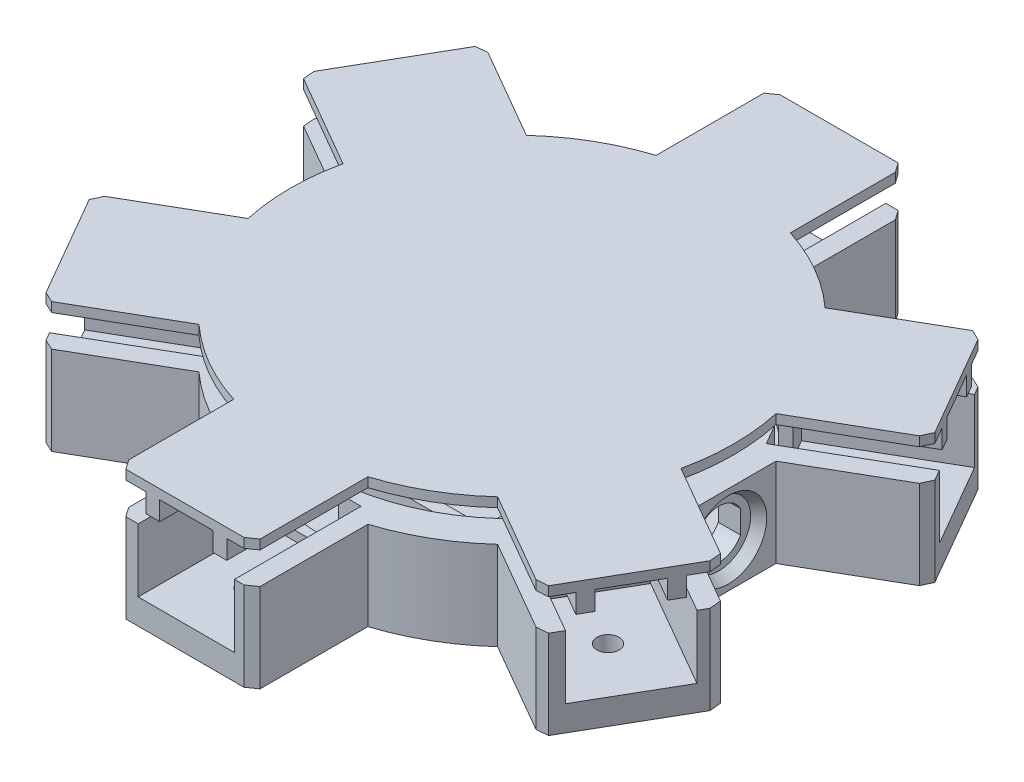
SolidWorks part; units mm, degrees
ref_plane "Front" through (0, 0, 0) normal (0, 0, 1) x (1, 0, 0)
ref_plane "Top" through (0, 0, 0) normal (0, 1, 0) x (1, 0, 0)
ref_plane "Right" through (0, 0, 0) normal (1, 0, 0) x (0, 0, -1)
sketch "Эскиз1" plane through (0, 0, 0) normal (0, 1, 0) x (1, 0, 0)
  line L0 (0, 0) -> (0, 74.8456) construction
  line L1 (63.5176, 45.4476) -> (11.5561, 15.4476) construction
  line L2 (-7.6, 77.7316) -> (7.6, 77.7316) construction
  line L3 (-7.6, 77.7316) -> (-7.6, 17.7316) construction
  line L4 (-7.6, 17.7316) -> (7.6, 17.7316) construction
  line L5 (7.6, 77.7316) -> (7.6, 17.7316) construction
  line L6 (0, 17.7316) -> (0, 77.7316) construction
  line L7 (-7.6, 47.7316) -> (7.6, 47.7316) construction
  line L8 (63.5176, 45.4476) -> (71.1176, 32.284) construction
  line L9 (0, 0) -> (64.8182, 37.4228) construction
  line L10 (71.1176, 32.284) -> (19.1561, 2.284) construction
  line L11 (11.5561, 15.4476) -> (19.1561, 2.284) construction
  line L12 (71.1176, -32.284) -> (19.1561, -2.284) construction
  line L13 (71.1176, -32.284) -> (63.5176, -45.4476) construction
  line L14 (0, 0) -> (64.8182, -37.4228) construction
  line L15 (63.5176, -45.4476) -> (11.5561, -15.4476) construction
  line L16 (19.1561, -2.284) -> (11.5561, -15.4476) construction
  line L17 (7.6, -77.7316) -> (7.6, -17.7316) construction
  line L18 (7.6, -77.7316) -> (-7.6, -77.7316) construction
  line L19 (0, 0) -> (0, -74.8456) construction
  line L20 (-7.6, -77.7316) -> (-7.6, -17.7316) construction
  line L21 (7.6, -17.7316) -> (-7.6, -17.7316) construction
  line L22 (-63.5176, -45.4476) -> (-11.5561, -15.4476) construction
  line L23 (-63.5176, -45.4476) -> (-71.1176, -32.284) construction
  line L24 (0, 0) -> (-64.8182, -37.4228) construction
  line L25 (-71.1176, -32.284) -> (-19.1561, -2.284) construction
  line L26 (-11.5561, -15.4476) -> (-19.1561, -2.284) construction
  line L27 (-71.1176, 32.284) -> (-19.1561, 2.284) construction
  line L28 (-71.1176, 32.284) -> (-63.5176, 45.4476) construction
  line L29 (0, 0) -> (-64.8182, 37.4228) construction
  line L30 (-63.5176, 45.4476) -> (-11.5561, 15.4476) construction
  line L31 (-19.1561, 2.284) -> (-11.5561, 15.4476) construction
  line L32 (0, 31.44) -> (-11.5561, 31.44) construction
  line L33 (-7.6, 31.44) -> (-7.6, 51.44)
  line L34 (-7.6, 51.44) -> (-10.6, 51.44)
  line L35 (-10.6, 51.44) -> (-10.6, 33.3563)
  line L36 (0, 31.44) -> (11.9132, 31.44) construction
  line L38 (7.6, 31.44) -> (7.6, 51.44)
  line L39 (7.6, 51.44) -> (10.6, 51.44)
  line L40 (10.6, 51.44) -> (10.6, 33.3563)
  line L42 (-7.6, 31.44) -> (7.6, 31.44)
  line L43 (39.2483, 34.8999) -> (23.5874, 25.858)
  line L44 (23.4278, 22.3018) -> (40.7483, 32.3018)
  line L45 (40.7483, 32.3018) -> (39.2483, 34.8999)
  line L46 (48.3483, 19.1382) -> (49.8483, 16.5401)
  line L47 (31.0278, 9.1382) -> (48.3483, 19.1382)
  line L48 (49.8483, 16.5401) -> (34.1874, 7.4983)
  line L49 (23.4278, 22.3018) -> (31.0278, 9.1382)
  line L50 (49.8483, -16.5401) -> (34.1874, -7.4983)
  line L51 (31.0278, -9.1382) -> (48.3483, -19.1382)
  line L52 (48.3483, -19.1382) -> (49.8483, -16.5401)
  line L53 (40.7483, -32.3018) -> (39.2483, -34.8999)
  line L54 (23.4278, -22.3018) -> (40.7483, -32.3018)
  line L55 (39.2483, -34.8999) -> (23.5874, -25.858)
  line L56 (31.0278, -9.1382) -> (23.4278, -22.3018)
  line L57 (10.6, -51.44) -> (10.6, -33.3563)
  line L58 (7.6, -31.44) -> (7.6, -51.44)
  line L59 (7.6, -51.44) -> (10.6, -51.44)
  line L60 (-7.6, -51.44) -> (-10.6, -51.44)
  line L61 (-7.6, -31.44) -> (-7.6, -51.44)
  line L62 (-10.6, -51.44) -> (-10.6, -33.3563)
  line L63 (7.6, -31.44) -> (-7.6, -31.44)
  line L64 (-39.2483, -34.8999) -> (-23.5874, -25.858)
  line L65 (-23.4278, -22.3018) -> (-40.7483, -32.3018)
  line L66 (-40.7483, -32.3018) -> (-39.2483, -34.8999)
  line L67 (-48.3483, -19.1382) -> (-49.8483, -16.5401)
  line L68 (-31.0278, -9.1382) -> (-48.3483, -19.1382)
  line L69 (-49.8483, -16.5401) -> (-34.1874, -7.4983)
  line L70 (-23.4278, -22.3018) -> (-31.0278, -9.1382)
  line L71 (-49.8483, 16.5401) -> (-34.1874, 7.4983)
  line L72 (-31.0278, 9.1382) -> (-48.3483, 19.1382)
  line L73 (-48.3483, 19.1382) -> (-49.8483, 16.5401)
  line L74 (-40.7483, 32.3018) -> (-39.2483, 34.8999)
  line L75 (-23.4278, 22.3018) -> (-40.7483, 32.3018)
  line L76 (-39.2483, 34.8999) -> (-23.5874, 25.858)
  line L77 (-31.0278, 9.1382) -> (-23.4278, 22.3018)
  line L78 (34.1874, 7.4983) -> (34.1874, -7.4983)
  line L79 (29.1874, 6.9352) -> (29.1874, -6.9352)
  arc A0 (29.1874, 6.9352) -> (29.1874, -6.9352) centre (0, 0) ccw
  arc A1 (-10.6, 33.3563) -> (-23.5874, 25.858) centre (0, 0) ccw
  arc A2 (-34.1874, 7.4983) -> (-34.1874, -7.4983) centre (0, 0) ccw
  arc A3 (23.5874, 25.858) -> (10.6, 33.3563) centre (0, 0) ccw
  arc A4 (-23.5874, -25.858) -> (-10.6, -33.3563) centre (0, 0) ccw
  arc A5 (10.6, -33.3563) -> (23.5874, -25.858) centre (0, 0) ccw
  point P3 (0, 47.7316)
  dimension "D2" = 60
  dimension "D3" = 70
  dimension "D1" = 15.2
  dimension "D4" = 60
  dimension "D6" = 20
  dimension "D7" = 3
  dimension "D8" = 3
  dimension "D9" = 31.44
  dimension "D10" = 6
  dimension "D11" = 5
  dimension "D5" = 6
extrude "Бобышка-Вытянуть1" add sketch "Эскиз1" along normal blind 12
sketch "Эскиз2" plane through (0, 0, 0) normal (0, -1, 0) x (1, 0, 0)
  line L0 (-10.6, 51.44) -> (10.6, 51.44)
  line L1 (10.6, 51.44) -> (10.6, 33.3563)
  line L2 (-10.6, 51.44) -> (-10.6, 33.3563)
  line L3 (-23.5874, 25.858) -> (-39.2483, 34.8999)
  line L4 (-39.2483, 34.8999) -> (-49.8483, 16.5401)
  line L5 (-49.8483, 16.5401) -> (-34.1874, 7.4983)
  line L6 (-34.1874, -7.4983) -> (-49.8483, -16.5401)
  line L7 (-49.8483, -16.5401) -> (-48.3483, -19.1382)
  line L8 (-48.3483, -19.1382) -> (-39.2483, -34.8999)
  line L9 (-39.2483, -34.8999) -> (-23.5874, -25.858)
  line L10 (-10.6, -33.3563) -> (-10.6, -51.44)
  line L11 (-10.6, -51.44) -> (10.6, -51.44)
  line L12 (10.6, -51.44) -> (10.6, -33.3563)
  line L13 (23.5874, -25.858) -> (39.2483, -34.8999)
  line L14 (39.2483, -34.8999) -> (49.8483, -16.5401)
  line L15 (49.8483, -16.5401) -> (34.1874, -7.4983)
  line L16 (34.1874, -7.4983) -> (34.1874, 7.4983)
  line L17 (34.1874, 7.4983) -> (49.8483, 16.5401)
  line L18 (49.8483, 16.5401) -> (39.2483, 34.8999)
  line L19 (39.2483, 34.8999) -> (23.5874, 25.858)
  arc A0 (-34.1874, 7.4983) -> (-34.1874, -7.4983) centre (0, 0) ccw
  arc A1 (-10.6, 33.3563) -> (-23.5874, 25.858) centre (0, 0) ccw
  arc A2 (23.5874, 25.858) -> (10.6, 33.3563) centre (0, 0) ccw
  arc A3 (-23.5874, -25.858) -> (-10.6, -33.3563) centre (0, 0) ccw
  arc A4 (10.6, -33.3563) -> (23.5874, -25.858) centre (0, 0) ccw
extrude "Бобышка-Вытянуть2" add sketch "Эскиз2" along normal blind 2
sketch "Эскиз3" plane through (0, 0, 0) normal (0, 1, 0) x (1, 0, 0)
  line L0 (0, 31.44) -> (0, 51.44) construction
  line L1 (-7.6, 51.44) -> (7.6, 51.44)
  line L2 (-7.6, 51.44) -> (-7.6, 31.44)
  line L3 (-7.6, 31.44) -> (7.6, 31.44)
  line L4 (7.6, 51.44) -> (7.6, 31.44)
  line L5 (40.7483, 32.3018) -> (48.3483, 19.1382)
  line L6 (40.7483, 32.3018) -> (23.4278, 22.3018)
  line L7 (23.4278, 22.3018) -> (31.0278, 9.1382)
  line L8 (48.3483, 19.1382) -> (31.0278, 9.1382)
  line L9 (27.2278, 15.72) -> (44.5483, 25.72) construction
  line L10 (48.3483, -19.1382) -> (40.7483, -32.3018)
  line L11 (48.3483, -19.1382) -> (31.0278, -9.1382)
  line L12 (31.0278, -9.1382) -> (23.4278, -22.3018)
  line L13 (40.7483, -32.3018) -> (23.4278, -22.3018)
  line L14 (27.2278, -15.72) -> (44.5483, -25.72) construction
  line L15 (7.6, -51.44) -> (-7.6, -51.44)
  line L16 (7.6, -51.44) -> (7.6, -31.44)
  line L17 (7.6, -31.44) -> (-7.6, -31.44)
  line L18 (-7.6, -51.44) -> (-7.6, -31.44)
  line L19 (0, -31.44) -> (0, -51.44) construction
  line L20 (-40.7483, -32.3018) -> (-48.3483, -19.1382)
  line L21 (-40.7483, -32.3018) -> (-23.4278, -22.3018)
  line L22 (-23.4278, -22.3018) -> (-31.0278, -9.1382)
  line L23 (-48.3483, -19.1382) -> (-31.0278, -9.1382)
  line L24 (-27.2278, -15.72) -> (-44.5483, -25.72) construction
  line L25 (-48.3483, 19.1382) -> (-40.7483, 32.3018)
  line L26 (-48.3483, 19.1382) -> (-31.0278, 9.1382)
  line L27 (-31.0278, 9.1382) -> (-23.4278, 22.3018)
  line L28 (-40.7483, 32.3018) -> (-23.4278, 22.3018)
  line L29 (-27.2278, 15.72) -> (-44.5483, 25.72) construction
  circle A0 centre (0, 41.44) radius 1.75
  circle A1 centre (35.8881, 20.72) radius 1.75
  circle A2 centre (35.8881, -20.72) radius 1.75
  circle A3 centre (0, -41.44) radius 1.75
  circle A4 centre (-35.8881, -20.72) radius 1.75
  circle A5 centre (-35.8881, 20.72) radius 1.75
  dimension "D1" = 3.5
  dimension "D2" = 6
extrude "Бобышка-Вытянуть3" add sketch "Эскиз3" along normal blind 2
sketch "Эскиз4" plane through (0, 12, 0) normal (0, 1, 0) x (1, 0, 0)
  line L0 (0, 31.44) -> (0, 28.9927) construction
  line L1 (7.6, 31.44) -> (-7.6, 31.44) construction
  line L2 (25.6064, 19.4027) -> (29.6064, 12.4745)
  line L3 (-4, 31.8771) -> (4, 31.8771)
  line L4 (-4, 31.8771) -> (-4, 28.5556)
  line L5 (-4, 28.5556) -> (4, 28.5556)
  line L6 (4, 31.8771) -> (4, 28.5556)
  line L7 (0, 28.5556) -> (0, 31.8771) construction
  line L8 (-4, 30.2163) -> (4, 30.2163) construction
  line L9 (25.6064, 19.4027) -> (22.7298, 17.7419)
  line L10 (22.7298, 17.7419) -> (26.7298, 10.8137)
  line L11 (29.6064, 12.4745) -> (26.7298, 10.8137)
  line L12 (27.2278, 15.72) -> (25.1084, 14.4963) construction
  line L13 (24.7298, 14.2778) -> (27.6064, 15.9386) construction
  line L14 (24.1681, 18.5723) -> (28.1681, 11.6441) construction
  line L15 (29.6064, -12.4745) -> (25.6064, -19.4027)
  line L16 (29.6064, -12.4745) -> (26.7298, -10.8137)
  line L17 (26.7298, -10.8137) -> (22.7298, -17.7419)
  line L18 (25.6064, -19.4027) -> (22.7298, -17.7419)
  line L19 (27.2278, -15.72) -> (25.1084, -14.4963) construction
  line L20 (24.7298, -14.2778) -> (27.6064, -15.9386) construction
  line L21 (28.1681, -11.6441) -> (24.1681, -18.5723) construction
  line L22 (4, -31.8771) -> (-4, -31.8771)
  line L23 (4, -31.8771) -> (4, -28.5556)
  line L24 (4, -28.5556) -> (-4, -28.5556)
  line L25 (-4, -31.8771) -> (-4, -28.5556)
  line L26 (0, -31.44) -> (0, -28.9927) construction
  line L27 (0, -28.5556) -> (0, -31.8771) construction
  line L28 (4, -30.2163) -> (-4, -30.2163) construction
  line L29 (-25.6064, -19.4027) -> (-29.6064, -12.4745)
  line L30 (-25.6064, -19.4027) -> (-22.7298, -17.7419)
  line L31 (-22.7298, -17.7419) -> (-26.7298, -10.8137)
  line L32 (-29.6064, -12.4745) -> (-26.7298, -10.8137)
  line L33 (-27.2278, -15.72) -> (-25.1084, -14.4963) construction
  line L34 (-24.7298, -14.2778) -> (-27.6064, -15.9386) construction
  line L35 (-24.1681, -18.5723) -> (-28.1681, -11.6441) construction
  line L36 (-29.6064, 12.4745) -> (-25.6064, 19.4027)
  line L37 (-29.6064, 12.4745) -> (-26.7298, 10.8137)
  line L38 (-26.7298, 10.8137) -> (-22.7298, 17.7419)
  line L39 (-25.6064, 19.4027) -> (-22.7298, 17.7419)
  line L40 (-27.2278, 15.72) -> (-25.1084, 14.4963) construction
  line L41 (-24.7298, 14.2778) -> (-27.6064, 15.9386) construction
  line L42 (-28.1681, 11.6441) -> (-24.1681, 18.5723) construction
  point P5 (0, 30.2163)
  point P13 (26.1681, 15.1082)
  point P24 (26.1681, -15.1082)
  point P35 (0, -30.2163)
  point P46 (-26.1681, -15.1082)
  point P57 (-26.1681, 15.1082)
  dimension "D1" = 8
  dimension "D2" = 6
extrude "Вырез-Вытянуть1" cut sketch "Эскиз4" against normal blind 8.5
sketch "Эскиз5" plane through (34.1874, 0, 0) normal (1, 0, 0) x (0, 0, -1)
  line L0 (0, 12) -> (0, -2) construction
  line L1 (-7.4983, 12) -> (7.4983, 12) construction
  line L2 (7.4983, -2) -> (-7.4983, -2) construction
  line L3 (-3.4, 6.8062) -> (-3.4, 3.1938)
  line L4 (3.4, 6.8062) -> (3.4, 3.1938)
  arc A0 (-3.4, 3.1938) -> (3.4, 3.1938) centre (0, 5) ccw
  arc A1 (3.4, 6.8062) -> (-3.4, 6.8062) centre (0, 5) ccw
  dimension "D1" = 7.7
  dimension "D2" = 3.4
  dimension "D3" = 3.4
extrude "Вырез-Вытянуть2" cut sketch "Эскиз5" against normal blind 5
sketch "Эскиз7" plane through (34.1874, 0, 0) normal (1, 0, 0) x (0, 0, -1)
  circle A0 centre (0, 5) radius 5
  dimension "D1" = 10
extrude "Вырез-Вытянуть3" cut sketch "Эскиз7" against normal blind 1.5
chamfer "Фаска1" distance 1.5 angle 35 1 edges at (34.1874, 5, -5)
sketch "Эскиз8" plane through (29.1874, 0, 0) normal (-1, 0, 0) x (0, 0, 1)
  circle A0 centre (0, 5) radius 6.25
  dimension "D1" = 12.5
extrude "Вырез-Вытянуть4" cut sketch "Эскиз8" along normal blind 5
sketch "Эскиз6" plane through (0, 0, 0) normal (0, 1, 0) x (1, 0, 0)
  line L1 (-13, 17.5) -> (13, 17.5)
  line L2 (-13, 17.5) -> (-13, -17.5)
  line L3 (-13, -17.5) -> (13, -17.5)
  line L4 (13, 17.5) -> (13, -17.5)
  line L5 (0, -17.5) -> (0, 17.5) construction
  line L6 (-13, 0) -> (13, 0) construction
  line L7 (-15, 19.5) -> (15, 19.5)
  line L8 (-15, 19.5) -> (-15, -19.5)
  line L9 (-15, -19.5) -> (15, -19.5)
  line L10 (15, 19.5) -> (15, -19.5)
  line L11 (0, -19.5) -> (0, 19.5) construction
  line L12 (-15, 0) -> (15, 0) construction
  point P0 (0, 0)
  point P4 (0, 0)
  dimension "D1" = 26
  dimension "D2" = 35
  dimension "D3" = 0
  dimension "D4" = 0
  dimension "D5" = 2
  dimension "D6" = 2
extrude "Бобышка-Вытянуть4" add sketch "Эскиз6" along normal blind 5
sketch "Эскиз9" plane through (0, 0, 0) normal (0, 1, 0) x (1, 0, 0)
  line L0 (-13, -17.5) -> (13, -17.5) construction
  line L1 (-13, 17.5) -> (-11.6, 17.5)
  line L2 (-13, 17.5) -> (-13, -17.5)
  line L3 (-13, -17.5) -> (-11.6, -17.5)
  line L4 (-11.6, 17.5) -> (-11.6, -16.1)
  line L5 (-13, -17.5) -> (13, -17.5) construction
  line L6 (13, 17.5) -> (11.6, 17.5)
  line L7 (13, 17.5) -> (13, -17.5)
  line L8 (13, -17.5) -> (11.6, -17.5)
  line L9 (11.6, 17.5) -> (11.6, -16.1)
  line L11 (-11.6, -17.5) -> (11.6, -17.5)
  line L13 (-11.6, -16.1) -> (11.6, -16.1)
  dimension "D1" = 1.4
  dimension "D2" = 1.4
  dimension "D3" = 1.4
extrude "Бобышка-Вытянуть5" add sketch "Эскиз9" along normal blind 3.5
chamfer "Фаска2" distance 1.5 angle 35 2 edges at (13, 4.25, -17.5) (-13, 4.25, -17.5)
sketch "Эскиз10" plane through (0, 0, 0) normal (0, 1, 0) x (1, 0, 0)
  circle A0 centre (0, 41.44) radius 1.75
  circle A1 centre (35.8881, 20.72) radius 1.75
  circle A2 centre (35.8881, -20.72) radius 1.75
  circle A3 centre (0, -41.44) radius 1.75
  circle A4 centre (-35.8881, -20.72) radius 1.75
  circle A5 centre (-35.8881, 20.72) radius 1.75
  dimension "D1" = 6
extrude "Вырез-Вытянуть5" cut sketch "Эскиз10" against normal through all
chamfer "Фаска3" distance 1.5 angle 35 12 edges at (-49.8483, 5, -16.5401) (-39.2483, 5, -34.8999) (39.2483, 5, 34.8999) (10.6, 5, 51.44) (-10.6, 5, 51.44) (-49.8483, 5, 16.5401) (-39.2483, 5, 34.8999) (49.8483, 5, 16.5401) (49.8483, 5, -16.5401) (39.2483, 5, -34.8999) (10.6, 5, -51.44) (-10.6, 5, -51.44)
ref_plane "Плоскость1" through (0, 17, 0) normal (0, 1, 0) x (1, 0, 0)
sketch "Эскиз11" plane through (0, 17, 0) normal (0, 1, 0) x (1, 0, 0)
  line L0 (0, 31.44) -> (0, 53.1863) construction
  line L1 (-7.6, 31.44) -> (7.6, 31.44) construction
  line L2 (-10.6, 50.3897) -> (-10.6, 33.3563)
  line L3 (-10.6, 50.3897) -> (-9.1, 51.44)
  line L4 (-9.1, 51.44) -> (9.5497, 51.44)
  line L5 (9.5497, 51.44) -> (10.6, 49.94)
  line L6 (10.6, 49.94) -> (10.6, 33.3563)
  line L7 (38.3388, 34.3747) -> (23.5874, 25.858)
  line L8 (38.3388, 34.3747) -> (39.9983, 33.6008)
  line L9 (39.9983, 33.6008) -> (49.3232, 17.4497)
  line L10 (49.3232, 17.4497) -> (48.5493, 15.7901)
  line L11 (48.5493, 15.7901) -> (34.1874, 7.4983)
  line L12 (48.9388, -16.015) -> (34.1874, -7.4983)
  line L13 (48.9388, -16.015) -> (49.0983, -17.8392)
  line L14 (49.0983, -17.8392) -> (39.7735, -33.9903)
  line L15 (39.7735, -33.9903) -> (37.9493, -34.1499)
  line L16 (37.9493, -34.1499) -> (23.5874, -25.858)
  line L17 (10.6, -50.3897) -> (10.6, -33.3563)
  line L18 (10.6, -50.3897) -> (9.1, -51.44)
  line L19 (9.1, -51.44) -> (-9.5497, -51.44)
  line L20 (-9.5497, -51.44) -> (-10.6, -49.94)
  line L21 (-10.6, -49.94) -> (-10.6, -33.3563)
  line L22 (-38.3388, -34.3747) -> (-23.5874, -25.858)
  line L23 (-38.3388, -34.3747) -> (-39.9983, -33.6008)
  line L24 (-39.9983, -33.6008) -> (-49.3232, -17.4497)
  line L25 (-49.3232, -17.4497) -> (-48.5493, -15.7901)
  line L26 (-48.5493, -15.7901) -> (-34.1874, -7.4983)
  line L27 (-48.9388, 16.015) -> (-34.1874, 7.4983)
  line L28 (-48.9388, 16.015) -> (-49.0983, 17.8392)
  line L29 (-49.0983, 17.8392) -> (-39.7735, 33.9903)
  line L30 (-39.7735, 33.9903) -> (-37.9493, 34.1499)
  line L31 (-37.9493, 34.1499) -> (-23.5874, 25.858)
  arc A0 (-34.1874, 7.4983) -> (-34.1874, -7.4983) centre (0, 0) ccw
  arc A1 (-10.6, 33.3563) -> (-23.5874, 25.858) centre (0, 0) ccw
  arc A2 (23.5874, 25.858) -> (10.6, 33.3563) centre (0, 0) ccw
  arc A3 (34.1874, -7.4983) -> (34.1874, 7.4983) centre (0, 0) ccw
  arc A4 (10.6, -33.3563) -> (23.5874, -25.858) centre (0, 0) ccw
  arc A5 (-23.5874, -25.858) -> (-10.6, -33.3563) centre (0, 0) ccw
  dimension "D1" = 6
sketch "Эскиз12" plane through (0, 17, 0) normal (0, 1, 0) x (1, 0, 0)
  line L0 (-9.1, 51.44) -> (9.5497, 51.44) construction
  line L1 (-6.4, 51.44) -> (-4.2, 51.44)
  line L2 (-6.4, 51.44) -> (-6.4, 32.44)
  line L4 (6.4, 51.44) -> (6.4, 32.44)
  line L6 (0, 31.44) -> (0, 53.1863) construction
  line L7 (-4.2, 51.44) -> (-4.2, 32.44)
  line L8 (4.2, 51.44) -> (4.2, 32.44)
  line L9 (4.2, 51.44) -> (6.4, 51.44)
  line L11 (41.3483, 31.2626) -> (42.4483, 29.3573)
  line L12 (41.3483, 31.2626) -> (24.8939, 21.7626)
  line L14 (47.7483, 20.1774) -> (31.2939, 10.6774)
  line L15 (42.4483, 29.3573) -> (25.9939, 19.8573)
  line L16 (46.6483, 22.0827) -> (30.1939, 12.5827)
  line L17 (46.6483, 22.0827) -> (47.7483, 20.1774)
  line L19 (47.7483, -20.1774) -> (46.6483, -22.0827)
  line L20 (47.7483, -20.1774) -> (31.2939, -10.6774)
  line L22 (41.3483, -31.2626) -> (24.8939, -21.7626)
  line L23 (46.6483, -22.0827) -> (30.1939, -12.5827)
  line L24 (42.4483, -29.3573) -> (25.9939, -19.8573)
  line L25 (42.4483, -29.3573) -> (41.3483, -31.2626)
  line L27 (6.4, -51.44) -> (4.2, -51.44)
  line L28 (6.4, -51.44) -> (6.4, -32.44)
  line L30 (-6.4, -51.44) -> (-6.4, -32.44)
  line L31 (4.2, -51.44) -> (4.2, -32.44)
  line L32 (-4.2, -51.44) -> (-4.2, -32.44)
  line L33 (-4.2, -51.44) -> (-6.4, -51.44)
  line L35 (-41.3483, -31.2626) -> (-42.4483, -29.3573)
  line L36 (-41.3483, -31.2626) -> (-24.8939, -21.7626)
  line L38 (-47.7483, -20.1774) -> (-31.2939, -10.6774)
  line L39 (-42.4483, -29.3573) -> (-25.9939, -19.8573)
  line L40 (-46.6483, -22.0827) -> (-30.1939, -12.5827)
  line L41 (-46.6483, -22.0827) -> (-47.7483, -20.1774)
  line L43 (-47.7483, 20.1774) -> (-46.6483, 22.0827)
  line L44 (-47.7483, 20.1774) -> (-31.2939, 10.6774)
  line L46 (-41.3483, 31.2626) -> (-24.8939, 21.7626)
  line L47 (-46.6483, 22.0827) -> (-30.1939, 12.5827)
  line L48 (-42.4483, 29.3573) -> (-25.9939, 19.8573)
  line L49 (-42.4483, 29.3573) -> (-41.3483, 31.2626)
  line L51 (28.538, 8.4049) -> (25.9001, 7.628)
  line L52 (25.9001, -7.628) -> (28.538, -8.4049)
  line L53 (-6.4, 32.44) -> (-4.2, 32.44)
  line L54 (-7.6, 31.44) -> (7.6, 31.44) construction
  line L55 (24.8939, 21.7626) -> (25.9939, 19.8573)
  line L56 (31.2939, -10.6774) -> (30.1939, -12.5827)
  line L57 (6.4, -32.44) -> (4.2, -32.44)
  line L58 (-24.8939, -21.7626) -> (-25.9939, -19.8573)
  line L59 (-31.2939, 10.6774) -> (-30.1939, 12.5827)
  line L60 (4.2, 32.44) -> (6.4, 32.44)
  line L61 (30.1939, 12.5827) -> (31.2939, 10.6774)
  line L62 (25.9939, -19.8573) -> (24.8939, -21.7626)
  line L63 (-4.2, -32.44) -> (-6.4, -32.44)
  line L64 (-30.1939, -12.5827) -> (-31.2939, -10.6774)
  line L65 (-25.9939, 19.8573) -> (-24.8939, 21.7626)
  arc A0 (28.538, 8.4049) -> (28.538, -8.4049) centre (0, 0) ccw
  arc A1 (25.9001, 7.628) -> (25.9001, -7.628) centre (0, 0) ccw
  dimension "D6" = 59.5
  dimension "D7" = 54
  dimension "D1" = 6.4
  dimension "D2" = 12.8
  dimension "D3" = 2.2
  dimension "D4" = 2.2
  dimension "D8" = 1
  dimension "D5" = 6
  dimension "D9" = 6
extrude "Бобышка-Вытянуть6" add sketch "Эскиз12" against normal blind 3 separate body
extrude "Бобышка-Вытянуть7" add sketch "Эскиз11" along normal blind 1.5
